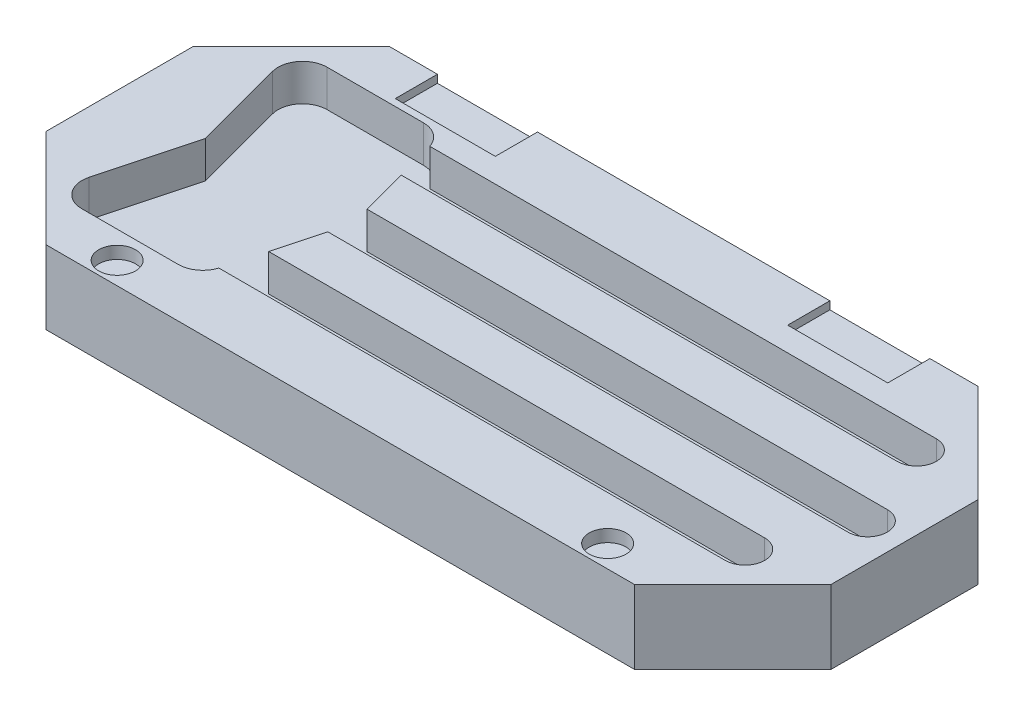
SolidWorks part; units mm, degrees
ref_plane "前视基准面" through (0, 0, 0) normal (0, 0, 1) x (1, 0, 0)
ref_plane "上视基准面" through (0, 0, 0) normal (0, 1, 0) x (1, 0, 0)
ref_plane "右视基准面" through (0, 0, 0) normal (1, 0, 0) x (0, 0, -1)
other "Configuration Table"
sketch "Sketch1" plane through (0, 0, 0) normal (0, 1, 0) x (1, 0, 0)
  line L0 (-101.6, -19.05) -> (-76.2, -44.45)
  line L1 (-76.2, 44.45) -> (76.2, 44.45)
  line L2 (-101.6, 19.05) -> (-101.6, -19.05)
  line L3 (-76.2, -44.45) -> (76.2, -44.45)
  line L4 (101.6, 19.05) -> (101.6, -19.05)
  line L5 (-101.6, 44.45) -> (101.6, -44.45) construction
  line L6 (-101.6, -44.45) -> (101.6, 44.45) construction
  line L7 (76.2, -44.45) -> (101.6, -19.05)
  line L8 (76.2, 44.45) -> (101.6, 19.05)
  line L9 (-76.2, 44.45) -> (-101.6, 19.05)
  arc A0 (101.6, -19.05) -> (76.2, -44.45) centre (76.2, -19.05) cw construction
  arc A1 (-76.2, -44.45) -> (-101.6, -19.05) centre (-76.2, -19.05) cw construction
  arc A2 (101.6, 19.05) -> (76.2, 44.45) centre (76.2, 19.05) ccw construction
  arc A3 (-101.6, 19.05) -> (-76.2, 44.45) centre (-76.2, 19.05) cw construction
  point P0 (0, 0)
  dimension "D3" = 25.4
  dimension "D1" = 88.9
  dimension "D2" = 203.2
extrude "Boss-Extrude1" add sketch "Sketch1" along normal blind 19.05
sketch "Sketch2" plane through (0, 19.05, 0) normal (0, 1, 0) x (1, 0, 0)
  line L0 (-76.2, 44.45) -> (-76.2, -44.45) construction
  line L1 (76.2, 44.45) -> (76.2, -44.45) construction
  line L2 (0, 44.45) -> (0, -44.45) construction
  line L3 (76.2, 44.45) -> (-76.2, 44.45) construction
  line L4 (-76.2, -44.45) -> (76.2, -44.45) construction
  line L5 (-76.2, 22.225) -> (82.55, 22.225) construction
  line L6 (-76.2, 27.305) -> (82.55, 27.305)
  line L7 (-76.2, 17.145) -> (82.55, 17.145)
  line L8 (92.075, 0) -> (-66.675, 0) construction
  line L9 (92.075, -5.08) -> (-66.675, -5.08)
  line L10 (92.075, 5.08) -> (-66.675, 5.08)
  line L11 (-76.2, -22.225) -> (82.55, -22.225) construction
  line L12 (-76.2, -17.145) -> (82.55, -17.145)
  line L13 (-76.2, -27.305) -> (82.55, -27.305)
  arc A0 (-76.2, 27.305) -> (-76.2, 17.145) centre (-76.2, 22.225) ccw
  arc A1 (82.55, 17.145) -> (82.55, 27.305) centre (82.55, 22.225) ccw
  arc A2 (92.075, -5.08) -> (92.075, 5.08) centre (92.075, 0) ccw
  arc A3 (-66.675, 5.08) -> (-66.675, -5.08) centre (-66.675, 0) ccw
  arc A4 (-76.2, -17.145) -> (-76.2, -27.305) centre (-76.2, -22.225) ccw
  arc A5 (82.55, -27.305) -> (82.55, -17.145) centre (82.55, -22.225) ccw
  point P16 (3.175, 22.225)
  point P21 (12.7, 0)
  point P29 (3.175, -22.225)
  point P36 (0, 0)
  point P37 (0, 0)
  point P38 (90.2045, 0)
  point P39 (76.2, 0)
  dimension "D7" = 5.08
  dimension "D8" = 5.08
  dimension "D9" = 5.08
  dimension "D1" = 22.225
  dimension "D2" = 22.225
  dimension "D3" = 22.225
  dimension "D4" = 158.75
  dimension "D5" = 158.75
  dimension "D6" = 158.75
  dimension "D10" = 15.875
extrude "Cut-Extrude1" cut sketch "Sketch2" against normal blind 9.525
sketch "Sketch3" plane through (0, 19.05, 0) normal (0, 1, 0) x (1, 0, 0)
  line L0 (-87.8824, 31.75) -> (-79.375, 0)
  line L1 (-79.375, 0) -> (-87.8824, -31.75)
  line L2 (-87.8824, -31.75) -> (-49.7824, -31.75)
  line L3 (-49.7824, -31.75) -> (-41.275, 0)
  line L4 (-41.275, 0) -> (-49.7824, 31.75)
  line L5 (-49.7824, 31.75) -> (-87.8824, 31.75)
  line L6 (92.075, 5.08) -> (-66.675, 5.08) construction
  line L7 (82.55, 27.305) -> (-76.2, 27.305) construction
  line L8 (-76.2, -27.305) -> (82.55, -27.305) construction
  arc A0 (-66.675, 5.08) -> (-66.675, -5.08) centre (-66.675, 0) ccw construction
  dimension "D1" = 150
  dimension "D2" = 75
  dimension "D3" = 12.7
  dimension "D4" = 4.445
  dimension "D5" = 4.445
  dimension "D6" = 38.1
extrude "Cut-Extrude2" cut sketch "Sketch3" against normal blind 9.525
fillet "Fillet2" radius 6.35 4 edges at (-49.7824, 14.2875, 31.75) (-49.7824, 14.2875, -31.75) (-87.8824, 14.2875, 31.75) (-87.8824, 14.2875, -31.75)
sketch "Sketch5" plane through (0, 19.05, 0) normal (0, 1, 0) x (1, 0, 0)
  line L0 (-76.2, -44.45) -> (76.2, -44.45) construction
  line L1 (-101.6, 19.05) -> (-101.6, -19.05) construction
  circle A0 centre (-63.5, -38.735) radius 4.7625
  circle A1 centre (63.5, -38.735) radius 4.7625
  dimension "D1" = 9.525
  dimension "D2" = 9.525
  dimension "D3" = 5.715
  dimension "D4" = 38.1
  dimension "D5" = 12.7
extrude "Cut-Extrude3" cut sketch "Sketch5" against normal blind 3.175
sketch "Sketch6" plane through (0, 19.05, 0) normal (0, 1, 0) x (1, 0, 0)
  line L0 (76.2, 44.45) -> (-76.2, 44.45) construction
  line L1 (-63.754, 44.45) -> (-37.846, 44.45)
  line L2 (-63.754, 44.45) -> (-63.754, 33.528)
  line L3 (-63.754, 33.528) -> (-37.846, 33.528)
  line L4 (-37.846, 44.45) -> (-37.846, 33.528)
  line L5 (-63.754, 44.45) -> (-37.846, 33.528) construction
  line L6 (-63.754, 33.528) -> (-37.846, 44.45) construction
  point P4 (-50.8, 38.989)
  dimension "D1" = 10.922
  dimension "D2" = 25.908
  dimension "D3" = 25.4
extrude "Cut-Extrude4" cut sketch "Sketch6" against normal blind 2.032
mirror "Mirror1" about plane through (0, 0, 0) normal (1, 0, 0) of "Cut-Extrude4"
